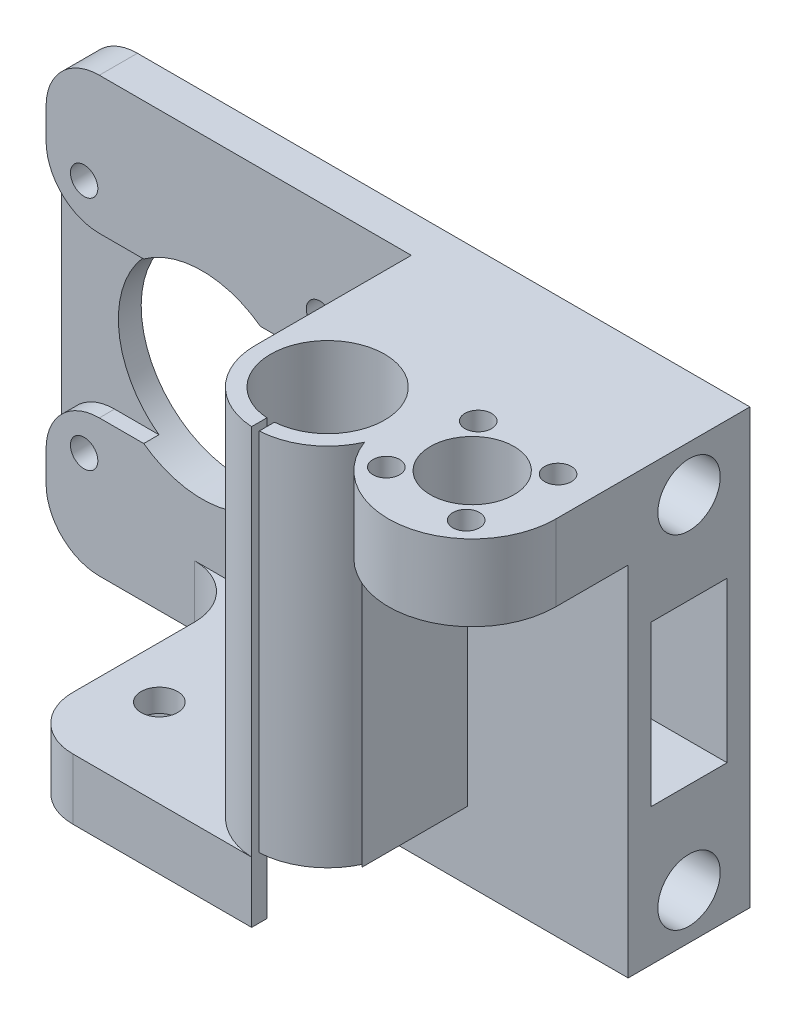
SolidWorks part; units mm, degrees
material "ABS"
ref_plane "Front Plane" through (0, 0, 0) normal (0, 0, 1) x (1, 0, 0)
ref_plane "Top Plane" through (0, 0, 0) normal (0, 1, 0) x (1, 0, 0)
ref_plane "Right Plane" through (0, 0, 0) normal (1, 0, 0) x (0, 0, -1)
sketch "Sketch2" plane through (0, 0, 0) normal (0, 1, 0) x (1, 0, 0)
  line L0 (0, 0) -> (0, -5)
  line L1 (0, -5) -> (48, -5)
  line L2 (48, -5) -> (48, -25.5)
  line L3 (57.5, -25.5) -> (48, -25.5) construction
  line L4 (87.5, -25.5) -> (87.5, 0)
  line L5 (87.5, 0) -> (0, 0)
  line L6 (57.5, -25.5) -> (76.5, -25.5) construction
  line L7 (66.1908, -29.3367) -> (66.1908, -25.5) construction
  line L8 (71.2515, -19.4623) -> (81.7485, -31.5377) construction
  line L9 (82.5377, -20.2515) -> (70.4623, -30.7485) construction
  line L10 (57.5, -25.5) -> (57.5, -34.9868) construction
  line L11 (57, -34.9868) -> (57.5, -34.9868) construction
  line L12 (57.5, -34.9868) -> (58, -34.9868) construction
  line L13 (57, -34.9868) -> (57, -32.9833)
  line L15 (58, -34.9868) -> (58, -32.9833)
  arc A0 (48, -25.5) -> (57, -34.9868) centre (57.5, -25.5) ccw
  circle A1 centre (76.5, -25.5) radius 5.5
  arc A2 (58, -32.9833) -> (57, -32.9833) centre (57.5, -25.5) ccw
  arc A3 (66.1908, -29.3367) -> (87.5, -25.5) centre (76.5, -25.5) ccw
  circle A4 centre (76.5, -25.5) radius 8 construction
  circle A5 centre (70.4623, -30.7485) radius 1.75
  circle A6 centre (82.5377, -20.2515) radius 1.75
  circle A7 centre (71.2515, -19.4623) radius 1.75
  circle A8 centre (81.7485, -31.5377) radius 1.75
  arc A9 (58, -34.9868) -> (66.1908, -29.3367) centre (57.5, -25.5) ccw
  dimension "D5" = 2
  dimension "D8" = 11
  dimension "D9" = 15
  dimension "D10" = 16
  dimension "D1" = 5.5
  dimension "D12" = 41
  dimension "D13" = 3.5
  dimension "D2" = 48
  dimension "D3" = 5
  dimension "D4" = 20.5
  dimension "D7" = 19
  dimension "D14" = 1
extrude "Boss-Extrude1" add sketch "Sketch2" along normal mid plane 57 contours L15 A9 A3 L4 L5 L0 L1 L2 A0 L13 A2 A1 A5 A6 A7 A8 region at (60.1326, 0, 12.0983)
sketch "Sketch3" plane through (0, 0, 0) normal (0, 0, 1) x (1, 0, 0)
  line L0 (0, 0) -> (88, 0) construction
  line L1 (66.4, 18.5) -> (88, 18.5)
  line L2 (66.4, 18.5) -> (66.4, -19.5)
  line L4 (88, 18.5) -> (88, -28.5)
  line L8 (57.1, -19.5) -> (66.4, -19.5)
  line L9 (57.1, -19.5) -> (57.1, -28.5)
  line L10 (57.1, -28.5) -> (88, -28.5)
  dimension "D4" = 47
  dimension "D1" = 88
  dimension "D2" = 18.5
  dimension "D3" = 21.6
  dimension "D5" = 9
  dimension "D6" = 9.3
extrude "Cut-Extrude1" cut sketch "Sketch3" along normal through all from offset 16
sketch "Sketch4" plane through (0, 0, 0) normal (0, 0, 1) x (1, 0, 0)
  line L0 (5, 15.5) -> (36, 15.5) construction
  line L1 (36, 15.5) -> (36, -15.5) construction
  line L2 (36, -15.5) -> (5, -15.5) construction
  line L3 (5, -15.5) -> (5, 15.5) construction
  line L4 (5, -15.5) -> (36, 15.5) construction
  circle A0 centre (5, 15.5) radius 1.8
  circle A1 centre (36, 15.5) radius 1.8
  circle A2 centre (5, -15.5) radius 1.8
  circle A3 centre (36, -15.5) radius 1.8
  circle A4 centre (20.5, 0) radius 13
  dimension "D1" = 31
  dimension "D2" = 3.6
  dimension "D5" = 26
  dimension "D3" = 15.5
  dimension "D4" = 5
extrude "Holes-for-motor" cut sketch "Sketch4" along normal through all
sketch "Sketch5" plane through (0, 0, 0) normal (0, 1, 0) x (1, 0, 0)
  line L0 (57.5, -34.9868) -> (57, -34.9868) construction
  line L1 (26.5, -34.9868) -> (26.5, -4.9868)
  line L2 (57.5, -25.5) -> (57.5, -34.9868) construction
  line L3 (26.5, -4.9868) -> (48, -4.9868)
  line L4 (48, -25.5) -> (48, -4.9868)
  line L5 (26.5, -34.9868) -> (57, -34.9868)
  circle A0 centre (57.5, -25.5) radius 9.5
  dimension "D2" = 19
  dimension "D1" = 31
  dimension "D3" = 57.5
  dimension "D4" = 25.5
  dimension "D5" = 30
  dimension "D6" = 0.5
extrude "Boss-Extrude2" add sketch "Sketch5" against normal blind 8 from offset 20.5 contours A0 L4 L3 L1 region at (37.6225, 0, 20.36) offset against normal yes
sketch "Sketch6" plane through (0, 0, 0) normal (1, 0, 0) x (0, 0, -1)
  line L0 (-3, 0) -> (0, 0) construction
  line L1 (-13, 10.5) -> (-3, 10.5)
  line L2 (-13, 10.5) -> (-13, -10.5)
  line L3 (-13, -10.5) -> (-3, -10.5)
  line L4 (-3, 10.5) -> (-3, -10.5)
  dimension "D1" = 10
  dimension "D2" = 21
  dimension "D3" = 3
extrude "Cut-Extrude3" cut sketch "Sketch6" along normal through all
hole_wizard "M4 Clearance Hole1" positions "Sketch8" profile "Sketch9" hole size "M4" standard "ANSI Metric" end condition through all
sketch "Sketch8" plane through (0, -20.5, 0) normal (0, 1, 0) x (1, 0, 0)
  line L0 (26.5, -34.9868) -> (57, -34.9868) construction
  line L2 (26.5, -34.9868) -> (26.5, -5) construction
  point P0 (33.2838, -23.3998)
  dimension "D1" = 11.587
  dimension "D2" = 6.7838
sketch "Sketch9" plane through (33.2838, -20.5, 23.3998) normal (1, 0, 0) x (0, 0, 1)
  line L0 (0, 0) -> (0, 8)
  line L1 (0, 8) -> (2.4, 8)
  line L2 (2.4, 8) -> (2.4, 0)
  line L5 (2.4, 0) -> (0, 0)
  line L11 (0, -6.35) -> (0, 107.95) construction
  dimension "Thru Hole Dia." = 4.8
  dimension "Thru Hole Depth" = 8
sketch "Sketch10" plane through (0, -20.5, 0) normal (0, 1, 0) x (1, 0, 0)
  line L0 (33.2838, -23.3998) -> (35.6838, -23.3998) construction
  line L1 (39.8407, -23.3998) -> (37.7623, -19.7998)
  line L2 (37.7623, -19.7998) -> (22.7623, -19.7998)
  line L5 (22.7623, -26.9998) -> (37.7623, -26.9998)
  line L6 (37.7623, -26.9998) -> (39.8407, -23.3998)
  line L7 (22.7623, -26.9998) -> (22.7623, -19.7998)
  line L10 (33.0053, -20.8391) -> (31.9661, -22.6391) [skipped]
  line L11 (31.9661, -24.1606) -> (33.0053, -25.9606) [skipped]
  circle A0 centre (35.6838, -23.3998) radius 3.6 construction
  circle A1 centre (33.2838, -23.3998) radius 2.4 construction
  dimension "D1" = 7.2
  dimension "D2" = 15
extrude "Cut-Extrude6" cut sketch "Sketch10" against normal blind 3.4 from offset 3 offset against normal yes
fillet "Fillet1" radius 7 6 edges at (0, -28.5, 2.5) (0, 28.5, 2.5) (26.5, -24.5, 34.9868) (0, 10.5, 4) (0, -10.5, 4) (26.5, -24.5, 5)
sketch "Sketch11" plane through (87.5, 0, 0) normal (1, 0, 0) x (0, 0, -1)
  line L0 (-8, 0) -> (-8, 22.5) construction
  line L1 (-8, -22.5) -> (-8, 0) construction
  line L2 (0, 0) -> (-8, 0) construction
  line L3 (-8, -22.5) -> (-8, -28.5) construction
  line L5 (-16, -28.5) -> (0, -28.5) construction
  circle A0 centre (-8, -22.5) radius 4.1
  circle A1 centre (-8, 22.5) radius 4.1
  dimension "D1" = 45
  dimension "D2" = 8.2
extrude "Cut-Extrude7" cut sketch "Sketch11" against normal blind 30
